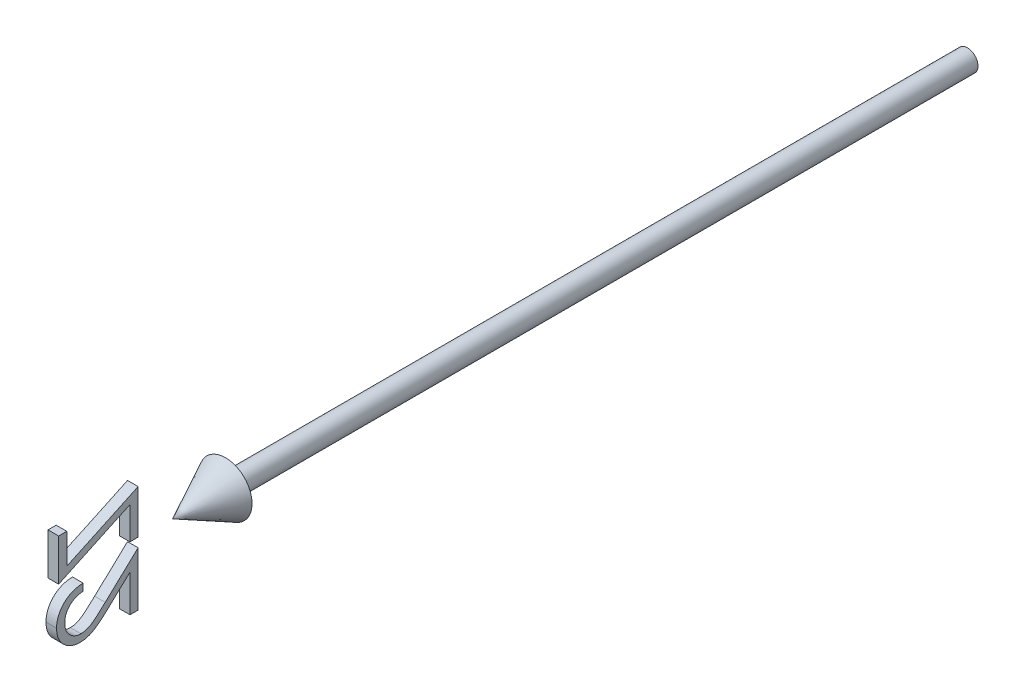
SolidWorks part; units mm, degrees
ref_plane "Front Plane" through (0, 0, 0) normal (0, 0, 1) x (1, 0, 0)
ref_plane "Top Plane" through (0, 0, 0) normal (0, 1, 0) x (1, 0, 0)
ref_plane "Right Plane" through (0, 0, 0) normal (1, 0, 0) x (0, 0, -1)
sketch "Sketch2" plane through (0, 0, 0) normal (0, 1, 0) x (1, 0, 0)
  line L0 (0, 41.95) -> (0, -114.4521) construction
  line L1 (-36.8894, 0) -> (41.4965, 0) construction
  line L2 (0, -150) -> (5, -140)
  line L3 (5, -140) -> (2, -140)
  line L4 (2, -140) -> (2, 0)
  line L5 (2, 0) -> (0, 0)
  line L6 (0, 0) -> (0, -150)
  dimension "D1" = 150
  dimension "D2" = 2
  dimension "D3" = 10
  dimension "D4" = 5
revolve "Revolve1" add sketch "Sketch2" angle 360 about L0
sketch "Sketch3" plane through (0, 0, 0) normal (1, 0, 0) x (0, -1, 0)
  line L0 (0, -101.5706) -> (0, -127.8138) construction
  line L1 (-10.1124, -157.5) -> (14.1256, -157.5) construction
  line L2 (-13.0255, 0) -> (32.001, 0) construction
  text T0 "Z2" font "Century Gothic" height 15
  dimension "D1" = 157.5
extrude "Boss-Extrude1" add sketch "Sketch3" against normal blind 1 and the other way blind 1 separate body
equation "\"D1@Sketch2\"=\"frame_arrow_length\""
equation "\"D2@Sketch2\"=\"frame_arrow_odA\"/2"
equation "\"D4@Sketch2\"=\"frame_arrow_head_od\""
equation "\"D3@Sketch2\"=\"frame_arrow_head_length\""
equation "\"frame_arrow_length\"=150"
equation "\"frame_arrow_head_length\"=10"
equation "\"frame_arrow_head_od\"=5"
equation "\"frame_arrow_odA\"=4"
equation "\"D1@Sketch3\"=\"frame_arrow_length\"*1.05"
